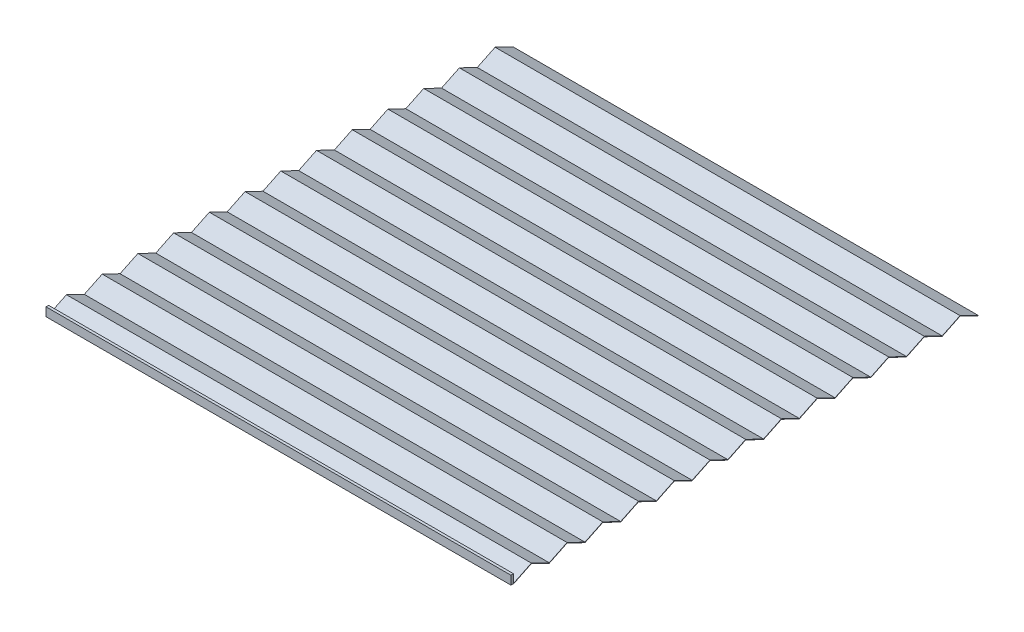
SolidWorks part; units mm, degrees
ref_plane "Front Plane" through (0, 0, 0) normal (0, 0, 1) x (1, 0, 0)
ref_plane "Top Plane" through (0, 0, 0) normal (0, 1, 0) x (1, 0, 0)
ref_plane "Right Plane" through (0, 0, 0) normal (1, 0, 0) x (0, 0, -1)
sketch "Sketch2" plane through (0, 0, 0) normal (0, 0, 1) x (1, 0, 0)
  line L1 (-270, 10) -> (270, 10)
  line L2 (-270, 10) -> (-270, 0)
  line L3 (-270, 0) -> (270, 0)
  line L4 (270, 10) -> (270, 0)
  point P4 (0, 0)
  dimension "D1" = 10
  dimension "D2" = 540
extrude "Boss-Extrude1" add sketch "Sketch2" along normal blind 3
sketch "Sketch3" plane through (270, 0, 0) normal (1, 0, 0) x (0, 0, -1)
  line L0 (0, 10) -> (539.3742, 10) construction
  line L1 (0, 0) -> (539.3742, 0) construction
  line L2 (539.3742, 10) -> (539.3742, 0) construction
  line L3 (0, 0) -> (20.7452, 10)
  line L4 (20.7452, 10) -> (41.4903, 0)
  line L5 (41.4903, 0) -> (62.2355, 10)
  line L6 (62.2355, 10) -> (82.9806, 0)
  line L7 (82.9806, 0) -> (103.7258, 10)
  line L8 (103.7258, 10) -> (124.471, 0)
  line L9 (124.471, 0) -> (145.2161, 10)
  line L10 (145.2161, 10) -> (165.9613, 0)
  line L11 (165.9613, 0) -> (186.7065, 10)
  line L12 (186.7065, 10) -> (207.4516, 0)
  line L13 (207.4516, 0) -> (228.1968, 10)
  line L14 (228.1968, 10) -> (248.9419, 0)
  line L15 (248.9419, 0) -> (269.6871, 10)
  line L16 (269.6871, 10) -> (290.4323, 0)
  line L17 (290.4323, 0) -> (311.1774, 10)
  line L18 (311.1774, 10) -> (331.9226, 0)
  line L20 (331.9226, 0) -> (352.6677, 10)
  line L21 (352.6677, 10) -> (373.4129, 0)
  line L22 (373.4129, 0) -> (394.1581, 10)
  line L23 (394.1581, 10) -> (414.9032, 0)
  line L24 (414.9032, 0) -> (435.6484, 10)
  line L25 (435.6484, 10) -> (456.3935, 0)
  line L26 (456.3935, 0) -> (477.1387, 10)
  line L27 (477.1387, 10) -> (497.8839, 0)
  line L28 (497.8839, 0) -> (518.629, 10)
  line L29 (518.629, 10) -> (539.3742, 0)
  line L30 (539.3742, 10) -> (539.3742, 0) construction
  point P1 (195.2172, 0)
extrude "Extrude-Thin1" add sketch "Sketch3" against normal through all thin thin type mid plane wall 0.5
